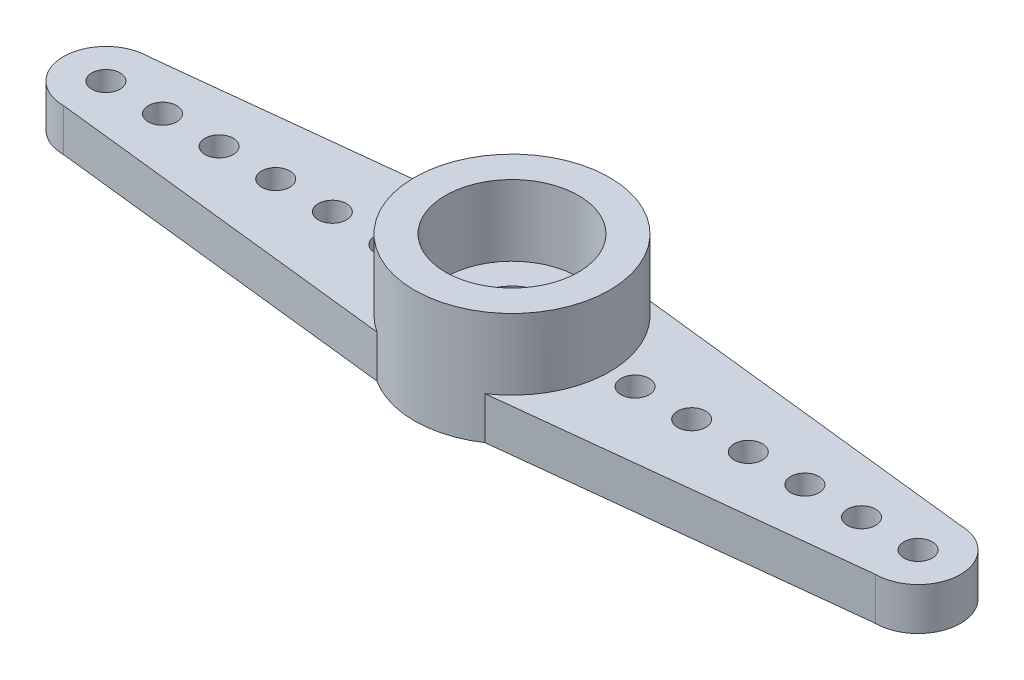
SolidWorks part; units mm, degrees
ref_plane "Front Plane" through (0, 0, 0) normal (0, 0, 1) x (1, 0, 0)
ref_plane "Top Plane" through (0, 0, 0) normal (0, 1, 0) x (1, 0, 0)
ref_plane "Right Plane" through (0, 0, 0) normal (1, 0, 0) x (0, 0, -1)
sketch "Sketch1" plane through (0, 0, 0) normal (0, 1, 0) x (1, 0, 0)
  line L0 (0, 0) -> (15.85, 0) construction
  line L1 (14.35, 1.5) -> (1.8797, 2.8929)
  line L3 (1.9132, -2.8709) -> (14.35, -1.5)
  line L4 (0, 3.45) -> (0, -3.45) construction
  line L5 (0, 0) -> (-15.85, 0) construction
  line L6 (-14.35, -1.5) -> (-1.8797, -2.8929)
  line L7 (-1.9132, 2.8709) -> (-14.35, 1.5)
  arc A0 (1.8797, 2.8929) -> (-1.9132, 2.8709) centre (0, 0) ccw
  circle A1 centre (0, 0) radius 1.275 construction
  circle A2 centre (0, 0) radius 2.35
  circle A4 centre (12.35, 0) radius 0.5
  circle A5 centre (14.35, 0) radius 0.5
  circle A6 centre (10.35, 0) radius 0.5
  circle A7 centre (8.35, 0) radius 0.5
  circle A9 centre (6.35, 0) radius 0.5
  circle A10 centre (4.35, 0) radius 0.5
  arc A11 (14.35, -1.5) -> (14.35, 1.5) centre (14.35, 0) ccw
  circle A15 centre (-12.35, 0) radius 0.5
  circle A16 centre (-14.35, 0) radius 0.5
  circle A17 centre (-10.35, 0) radius 0.5
  circle A18 centre (-8.35, 0) radius 0.5
  circle A19 centre (-6.35, 0) radius 0.5
  circle A20 centre (-4.35, 0) radius 0.5
  arc A21 (-14.35, 1.5) -> (-14.35, -1.5) centre (-14.35, 0) ccw
  arc A22 (-1.8797, -2.8929) -> (1.9132, -2.8709) centre (0, 0) ccw
  dimension "D1" = 14.35
  dimension "D2" = 2.55
  dimension "D3" = 4.7
  dimension "D4" = 6.9
sketch3d "3DSketch2" plane through (0, 0, 0) normal (0, 0, 1) x (1, 0, 0)
  dimension "D1" = 1.5
sketch "Sketch2" plane through (0, 1.5, 0) normal (0, 1, 0) x (1, 0, 0)
  circle A0 centre (0, 0) radius 1.275
  circle A1 centre (0, 0) radius 2.35
  circle A2 centre (0, 0) radius 3.45
extrude "Boss-Extrude3" add sketch "Sketch2" against normal blind 0.5 separate body contours A1 A0 region at (-2.2835, 1.5, 0)
extrude "Boss-Extrude5" add sketch "Sketch2<7>" along normal blind 2.5 separate body contours A2 A1 region at (-3.3524, 1.5, 0)
sketch "Sketch2<7>" plane through (0, 1.5, 0) normal (0, 1, 0) x (1, 0, 0) same geometry as "Sketch2"
extrude "Boss-Extrude6" add sketch "Sketch1" along normal blind 1.5
